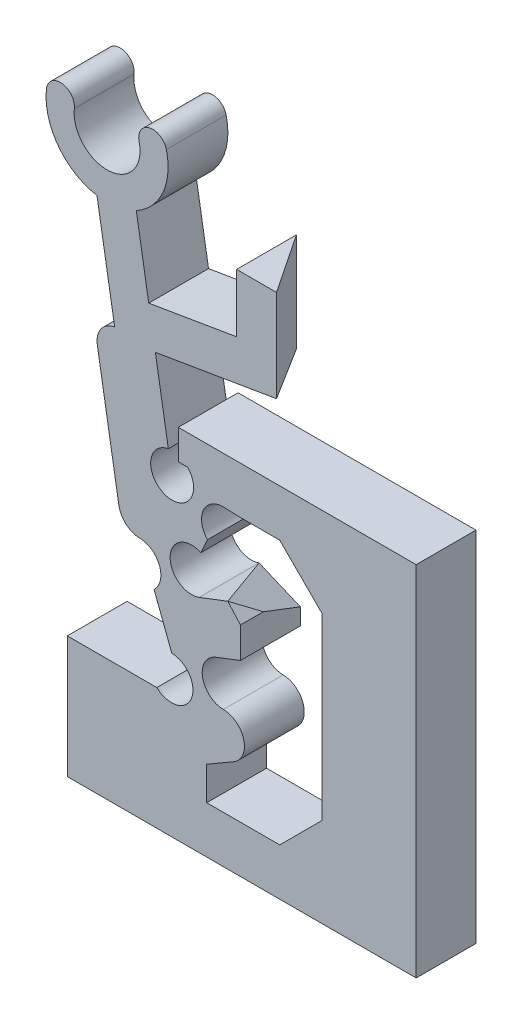
SolidWorks part; units mm, degrees
ref_plane "Front Plane" through (0, 0, 0) normal (0, 0, 1) x (1, 0, 0)
ref_plane "Top Plane" through (0, 0, 0) normal (0, 1, 0) x (1, 0, 0)
ref_plane "Right Plane" through (0, 0, 0) normal (1, 0, 0) x (0, 0, -1)
sketch "Sketch-SkeletonConfigUp" plane through (0, 0, 0) normal (0, 0, 1) x (1, 0, 0)
  line L0 (0, 0) -> (0, -50000) construction
  line L1 (0, 0) -> (4.5811, 6.2164) construction
  line L2 (9.8143, 13.3177) -> (4.5811, 13.945) construction
  line L3 (4.5811, 13.945) -> (2.9713, 10.4094) construction
  line L4 (2.9713, 10.4094) -> (4.5811, 6.2164) construction
  line L5 (4.5811, 13.945) -> (6.2429, 19.1409) construction
  line L6 (2.9713, 10.4094) -> (0.0405, 27.8193) construction
  line L7 (4.5811, 6.2164) -> (9.8143, 13.3177) construction
  line L8 (-587.3593, -797.0242) -> (9.8143, 13.3177) construction
  dimension "D2" = 7.7221
  dimension "D3" = 8.8212
  dimension "D4" = 5.2707
  dimension "D5" = 119.553
  dimension "D6" = 3.8848
  dimension "D7" = 5.4552
  dimension "D8" = 17.6549
  dimension "D9" = 4.4914
  dimension "D10" = 6.745
  dimension "D11" = 145.964
  dimension "D12" = 143.612
sketch "Sketch-SkeletonConfigDown" plane through (0, 0, 0) normal (0, 0, 1) x (1, 0, 0)
  line L0 (0, 0) -> (0, -50000) construction
  line L1 (0, 0) -> (4.5811, 6.2164) construction
  line L2 (9.8143, 13.3177) -> (4.5811, 13.945) construction
  line L3 (4.5811, 13.945) -> (6.1909, 10.4094) construction
  line L4 (6.1909, 10.4094) -> (4.5811, 6.2164) construction
  line L5 (4.5811, 13.945) -> (1.753, 18.6098) construction
  line L6 (6.1909, 10.4094) -> (-8.8652, 19.6294) construction
  line L7 (4.5811, 6.2164) -> (9.8143, 13.3177) construction
  line L8 (-589.9357, -800.5203) -> (9.8143, 13.3177) construction
  dimension "D2" = 7.7221
  dimension "D3" = 8.8212
  dimension "D4" = 5.2707
  dimension "D5" = 119.553
  dimension "D6" = 3.8848
  dimension "D7" = 5.4552
  dimension "D8" = 17.6549
  dimension "D9" = 4.4914
  dimension "D10" = 6.745
  dimension "D11" = 145.964
  dimension "D1" = 143.612
sketch "Sketch-SwitchBossUp" plane through (0, 0, 0) normal (0, 0, 1) x (1, 0, 0)
  line L0 (2.6478, 12.1123) -> (3.2566, 13.4492) construction
  line L1 (4.3447, 11.0125) -> (5.0768, 12.6205) construction
  line L2 (6.5405, 22.165) -> (6.5405, 25.0939)
  line L3 (6.5405, 25.0939) -> (8.5405, 25.0939)
  line L4 (8.5405, 25.0939) -> (8.5405, 20.4736)
  line L5 (4.5811, 13.945) -> (2.9713, 10.4094) construction
  line L7 (1.507, 25.1315) -> (2.1313, 21.4228)
  line L8 (-0.4652, 24.7995) -> (0.4213, 19.5329)
  line L9 (2.9713, 10.4094) -> (0.0405, 27.8193) construction
  line L10 (4.8917, 12.214) -> (3.0715, 13.0428) construction
  line L11 (-0.0396, 22.2712) -> (1.9326, 22.6032) construction
  line L13 (2.3961, 9.1174) -> (3.2891, 6.7916)
  line L14 (4.2633, 9.8343) -> (5.1563, 7.5084) construction
  line L15 (4.7098, 8.6713) -> (2.8426, 7.9545) construction
  line L16 (2.9713, 10.4094) -> (4.5811, 6.2164) construction
  line L17 (3.2566, 13.4492) -> (4.0854, 15.2694) construction
  line L18 (5.0768, 12.6205) -> (5.9056, 14.4407) construction
  line L19 (4.2853, 14.0796) -> (4.8769, 13.8103) construction
  line L20 (4.0854, 15.2694) -> (5.9056, 14.4407) construction
  line L21 (3.2566, 13.4492) -> (5.0768, 12.6205) construction
  line L22 (4.1667, 13.0349) -> (4.9955, 14.8551) construction
  line L23 (4.6678, 9.9058) -> (4.2913, 9.7612) construction
  line L24 (2.3961, 9.1174) -> (1.6793, 10.9845) construction
  line L25 (4.2633, 9.8343) -> (3.5464, 11.7014) construction
  line L26 (4.2633, 9.8343) -> (2.3961, 9.1174) construction
  line L27 (1.6793, 10.9845) -> (3.5464, 11.7014) construction
  line L28 (3.2891, 6.7916) -> (5.1563, 7.5084) construction
  line L29 (3.2891, 6.7916) -> (4.006, 4.9244) construction
  line L30 (5.1563, 7.5084) -> (5.8731, 5.6413) construction
  line L31 (4.006, 4.9244) -> (5.8731, 5.6413) construction
  line L32 (4.8845, 6.3329) -> (4.2777, 6.0999) construction
  line L36 (4.0854, 15.2694) -> (3.6136, 15.2694)
  line L40 (3.2747, 10.5259) -> (2.6679, 10.2929) construction
  line L43 (2.5363, 4.9244) -> (-1.9548, 4.9244)
  line L44 (-1.9548, 4.9244) -> (-1.9548, -1.1895)
  line L45 (-1.9548, -1.1895) -> (5.0405, -1.1895)
  line L46 (5.0405, 1.1715) -> (5.0405, 2.8478)
  line L51 (6.5405, 22.165) -> (2.1313, 21.4228)
  line L61 (6.6395, 14.4084) -> (6.6395, 16.7694) construction
  line L66 (0.0405, 27.8193) -> (0.0405, 50027.8193) construction
  line L73 (5.0768, 12.6205) -> (4.7428, 11.8869)
  line L74 (0.6325, 11.8929) -> (-0.448, 18.3116)
  line L75 (0.2173, 14.3595) -> (2.2273, 14.4682) construction
  line L76 (4.7428, 11.8869) -> (5.0768, 12.6205) construction
  line L77 (5.5047, 7.726) -> (5.1282, 7.5815) construction
  line L78 (4.6678, 9.9058) -> (6.094, 10.4534)
  line L79 (5.5047, 7.726) -> (6.4934, 8.1056)
  line L80 (6.094, 10.4534) -> (6.7341, 9.7424)
  line L81 (7.7675, 8.2601) -> (7.7675, -49991.7399) construction
  line L82 (2.1313, 21.4228) -> (3.1136, 15.5877) construction
  line L83 (3.1136, 15.5877) -> (2.4634, 19.4505)
  line L84 (2.4634, 19.4505) -> (8.5405, 20.4736)
  line L85 (6.9307, 9.5241) -> (7.7675, 8.5948) construction
  line L86 (6.4934, 8.1056) -> (6.7341, 8.198) construction
  line L88 (3.6136, 16.7694) -> (6.6395, 16.7694)
  line L90 (5.9056, 14.4407) -> (6.6395, 14.4084)
  line L92 (3.7762, 8.3129) -> (6.9307, 9.5241) construction
  line L93 (6.3942, 3.6294) -> (5.0405, 2.8478)
  line L94 (3.6136, 15.2694) -> (3.6136, 16.7694)
  line L95 (2.1313, 21.4228) -> (2.4634, 19.4505) construction
  line L96 (2.2974, 20.4367) -> (8.5405, 21.4876) construction
  line L97 (2.2974, 20.4367) -> (1.3112, 20.2707) construction
  line L98 (6.4934, 8.1056) -> (4.8199, 9.9642) construction
  line L99 (4.5811, 6.2164) -> (6.094, 10.4534) construction
  line L100 (4.5811, 6.2164) -> (8.5405, 8.3528) construction
  line L101 (4.5811, 6.2164) -> (6.9307, 9.5241) construction
  line L102 (4.5811, 6.2164) -> (8.5405, 7.1023) construction
  line L103 (8.5405, 20.4736) -> (8.5405, 8.3528) construction
  line L104 (6.9307, 9.5241) -> (7.7675, 8.5948) construction
  line L105 (6.7341, 8.198) -> (6.4934, 8.1056)
  line L106 (5.386, 8.3129) -> (8.5406, 7.1018) construction
  line L107 (6.1909, 10.4094) -> (4.5811, 6.2164) construction
  line L109 (6.9307, 8.2735) -> (7.7675, 8.5948) construction
  line L110 (7.7675, 8.5948) -> (6.9307, 8.2735) construction
  line L111 (6.7341, 9.7424) -> (6.7341, 8.198)
  line L112 (6.7341, 9.7424) -> (6.9307, 9.5241) construction
  line L113 (6.7341, 8.198) -> (6.9307, 8.2735) construction
  line L114 (6.9307, 8.2735) -> (6.7341, 8.198) construction
  line L115 (6.6395, 16.7694) -> (15.5467, 16.7694)
  line L116 (15.5467, 16.7694) -> (15.5467, -1.1895)
  line L117 (15.5467, -1.1895) -> (5.0405, -1.1895)
  line L118 (6.6395, 14.4084) -> (8.7032, 14.4084)
  line L119 (10.8245, 12.2871) -> (10.8245, 3.2928)
  line L120 (8.7032, 1.1715) -> (5.0405, 1.1715)
  line L121 (5.0405, -1.1895) -> (5.0405, 1.1715) construction
  line L122 (10.8245, 14.4084) -> (13.1856, 14.4084) construction
  line L123 (13.1856, 14.4084) -> (15.5467, 14.4084) construction
  line L124 (10.8245, 3.2928) -> (8.7032, 1.1715)
  line L125 (10.8245, 7.79) -> (15.5467, 7.79) construction
  line L126 (10.8245, 12.2871) -> (8.7032, 14.4084)
  line L127 (8.5405, 14.4084) -> (10.8245, 14.4084) construction
  line L128 (10.8245, 14.4084) -> (10.8245, 12.2871) construction
  line L129 (10.8245, 3.2928) -> (10.8245, 1.1715) construction
  line L130 (10.8245, 1.1715) -> (8.7032, 1.1715) construction
  arc A0 (1.507, 25.1315) -> (3.0168, 28.5383) centre (0.0405, 27.8193) ccw
  arc A1 (-0.4652, 24.7995) -> (-3.0011, 28.1713) centre (0.0405, 27.8193) cw
  arc A2 (-3.0011, 28.1713) -> (-1.6023, 28.0095) centre (-2.3017, 28.0904) cw
  arc A3 (3.0168, 28.5383) -> (1.648, 28.2077) centre (2.3324, 28.373) ccw
  arc A4 (-1.6023, 28.0095) -> (1.648, 28.2077) centre (0.0405, 27.8193) ccw
  arc A5 (3.2566, 13.4492) -> (4.0854, 15.2694) centre (3.304, 14.5264) ccw
  arc A6 (5.0768, 12.6205) -> (5.9056, 14.4407) centre (5.8582, 13.3635) cw
  arc A7 (2.3961, 9.1174) -> (1.6793, 10.9845) centre (1.6613, 9.9064) ccw
  arc A8 (3.5464, 11.7014) -> (4.2633, 9.8343) centre (4.2813, 10.9124) ccw
  arc A9 (3.2891, 6.7916) -> (4.006, 4.9244) centre (3.2711, 5.7135) cw
  arc A10 (5.1563, 7.5084) -> (5.8731, 5.6413) centre (5.8911, 6.7194) ccw
  arc A18 (1.6793, 10.9845) -> (0.6325, 11.8929) centre (1.6973, 12.0626) cw
  arc A19 (-0.448, 18.3116) -> (0.4213, 19.5329) centre (0.5973, 18.4876) cw
  arc A20 (3.2566, 13.4492) -> (3.1136, 15.5877) centre (3.304, 14.5264) cw
  arc A21 (4.006, 4.9244) -> (2.5363, 4.9244) centre (3.2711, 5.7135) cw
  arc A22 (5.8731, 5.6413) -> (6.3942, 3.6294) centre (5.8551, 4.5632) cw
  arc A24 (3.5464, 11.7014) -> (4.7428, 11.8869) centre (4.2813, 10.9124) cw
  arc A25 (4.2633, 9.8343) -> (4.6678, 9.9058) centre (4.2813, 10.9124) ccw
  arc A26 (5.1563, 7.5084) -> (5.5047, 7.726) centre (5.8911, 6.7194) cw
  arc A28 (6.3942, 3.6294) -> (5.2541, 3.668) centre (5.8551, 4.5632) cw construction
  point P44 (3.7762, 8.3129)
  point P53 (4.5811, 13.945)
  point P63 (2.9713, 10.4094)
  point P93 (0.9465, 22.4372)
  point P130 (0, 0)
  point P131 (0, 0)
  point P132 (0, 0)
  dimension "D1" = 2
  dimension "D2" = 2
  dimension "D3" = 2
  dimension "D4" = 2
  dimension "D5" = 2
  dimension "D6" = 0.65
  dimension "D7" = 2
  dimension "D8" = 42
  dimension "D9" = 0.5
  dimension "D10" = 5
  dimension "D11" = 8.5
  dimension "D12" = 120
  dimension "D13" = 1.5
  dimension "D14" = 10
  dimension "D15" = 45
  dimension "D16" = 42
  dimension "D17" = 42
  dimension "D18" = 3
extrude "Boss-SwitchMain" add sketch "Sketch-SwitchBossUp" along normal blind 3
sketch "Sketch1" plane through (0, 0, 0) normal (0, 0, -1) x (-1, 0, 0)
  line L0 (1.9548, 4.9244) -> (1.9548, -1.1895) construction
  line L1 (-4.628, -1.1895) -> (1.9548, -1.1895)
  line L2 (-4.628, -1.1895) -> (-4.628, 0.3105)
  line L3 (-4.628, 0.3105) -> (1.9548, 0.3105)
  line L4 (1.9548, -1.1895) -> (1.9548, 0.3105)
  line L5 (-3.6136, 16.7694) -> (-6.6395, 16.7694)
  line L6 (-2.5363, 4.9244) -> (1.9548, 4.9244)
  line L7 (-2.5363, 4.9244) -> (-2.5363, 3.4244)
  line L8 (-2.5363, 3.4244) -> (1.9548, 3.4244)
  line L9 (1.9548, 4.9244) -> (1.9548, 3.4244)
  line L10 (-6.6395, 16.7694) -> (-6.6395, 15.2694)
  line L12 (-6.6395, 15.2694) -> (-3.6136, 15.2694)
  line L13 (-5.128, -1.3839) -> (-5.128, 7.6731) construction
  line L14 (-3.6136, 15.2694) -> (-3.6136, 16.7694)
  line L18 (-3.6136, 16.7694) -> (-3.6136, 15.2694) construction
  line L19 (-5.128, -1.3839) -> (-5.128, 7.6731) construction
  line L20 (-6.6395, 16.7694) -> (-15.5467, 16.7694) construction
  line L21 (-6.6395, 14.4084) -> (-6.6395, 16.7694) construction
  point P16 (0, 0)
  point P21 (0, 0)
  point P22 (0, 0)
  dimension "D1" = 1.5
  dimension "D2" = 1.5
  dimension "D3" = 1.5
  dimension "D4" = 0.5
extrude "Boss-Flange Width" add sketch "Sketch1" along normal blind 6
ref_plane "Plane-Sta2Sit Groove" through (0.0405, 0, 0) normal (1, 0, 0) x (0, 0, -1)
ref_plane "Plane-Cam Face" through (-12.0395, 0, 0) normal (1, 0, 0) x (0, 0, -1)
ref_plane "Plane-FlangeTop" through (-7.0395, 0, 0) normal (1, 0, 0) x (0, 0, -1)
sketch "Sketch2" plane through (-7.0395, 0, 0) normal (1, 0, 0) x (0, 0, -1)
  line L0 (6, 15.2694) -> (-3, 15.2694) construction
  line L1 (6, 16.7694) -> (1, 16.7694)
  line L2 (6, 16.7694) -> (6, 15.2694)
  line L3 (6, 15.2694) -> (1, 15.2694)
  line L4 (1, 16.7694) -> (1, 15.2694)
  line L5 (6, 3.4244) -> (0, 3.4244) construction
  line L6 (6, 4.9244) -> (1, 4.9244)
  line L7 (6, 4.9244) -> (6, 3.4244)
  line L8 (6, 3.4244) -> (1, 3.4244)
  line L9 (1, 4.9244) -> (1, 3.4244)
  line L10 (-3, -1.1895) -> (6, -1.1895) construction
  line L11 (6, 0.3105) -> (1, 0.3105)
  line L12 (6, 0.3105) -> (6, -1.1895)
  line L13 (6, -1.1895) -> (1, -1.1895)
  line L14 (1, 0.3105) -> (1, -1.1895)
  line L15 (0, 10.4094) -> (0, 27.8193) construction
  dimension "D1" = 1
extrude "Boss-Flange Height" add sketch "Sketch2" along normal up to surface (11.6675 mm away)
sketch "Sketch-HolePositions" plane through (0, -1.1895, 0) normal (0, -1, 0) x (1, 0, 0)
  line L0 (-7.0395, -3.5) -> (4.628, -3.5) construction
  line L2 (4.628, -6) -> (4.628, 0) construction
  line L3 (-1.9548, -1) -> (-7.0395, -1) construction
  line L4 (-7.0395, -22.2167) -> (-7.0395, 22.2167) construction
  point P6 (-4.0395, -3.5)
  point P7 (1.628, -3.5)
  dimension "D1" = 3
  dimension "D2" = 3
  dimension "D3" = 2.5
sketch "Sketch6" plane through (0, -1.1895, 0) normal (0, -1, 0) x (-1, 0, 0)
  point P0 (4.0395, 3.5)
  point P3 (-1.628, 3.5)
hole_wizard "Tap Drill for M2x0.4 Tap1" positions "Sketch6" profile "Sketch5" hole size "M2x0.4" standard "ANSI Metric" end condition through all
sketch "Sketch5" plane through (-4.0395, -1.1895, -3.5) normal (1, 0, 0) x (0, 0, -1)
  line L0 (0, 0) -> (0, 30.2666)
  line L1 (0, 30.2666) -> (0.8, 30.2666)
  line L2 (0.8, 30.2666) -> (0.8, 0)
  line L5 (0.8, 0) -> (0, 0)
  line L11 (0, -6.35) -> (0, 107.95) construction
  dimension "Thru Hole Dia." = 1.6
  dimension "Thru Hole Depth" = 30.2666
sketch "Sketch9" plane through (0, -1.1895, 0) normal (0, -1, 0) x (1, 0, 0)
  point P0 (-4.0395, -3.5)
  point P3 (1.628, -3.5)
hole_wizard "M2 Clearance Hole2" positions "Sketch9" profile "Sketch8" hole size "M2" standard "ANSI Metric"
sketch "Sketch8" plane through (-4.0395, -1.1895, -3.5) normal (1, 0, 0) x (0, 0, -1)
  line L0 (0, 0) -> (0, 6.835)
  line L1 (0, 6.835) -> (1.2, 6.114)
  line L2 (1.2, 6.114) -> (1.2, 0)
  line L5 (1.2, 0) -> (0, 0)
  line L10 (0, 6.835) -> (-1.2, 6.114) construction
  line L11 (0, -6.35) -> (0, 107.95) construction
  dimension "Hole Dia." = 2.4
  dimension "Hole Depth" = 6.114
  dimension "Drill Angle" = 118
sketch "Sketch10" plane through (0, 16.7694, 0) normal (0, 1, 0) x (1, 0, 0)
  line L1 (6.6395, 6) -> (5.128, 6)
  line L2 (6.6395, 6) -> (6.6395, 3)
  line L3 (6.6395, 3) -> (5.128, 3)
  line L5 (4.628, 7) -> (4.628, 1) construction
  line L6 (3.6136, 1) -> (-7.0395, 1) construction
  line L7 (5.128, 6.25) -> (5.128, 1) construction
  line L8 (5.128, 6) -> (5.128, 3)
  point P1 (6.3963, 5.7235)
  point P13 (0, 0)
  dimension "D1" = 2
extrude "Cut-Flange Ramp Clearance" cut sketch "Sketch10" against normal up to next
sketch "Sketch-Measurements for Derailleur Ramps" plane through (0, 0, 0) normal (0, 0, 1) x (1, 0, 0)
  line L0 (2.4634, 19.4505) -> (2.1313, 21.4228)
  line L1 (2.2974, 20.4367) -> (1.3112, 20.2707)
  line L2 (2.9713, 10.4094) -> (0.0405, 27.8193) construction
  line L3 (1.3112, 20.2707) -> (-4.0257, 16.6658)
  line L4 (6.1909, 10.4094) -> (-8.8652, 19.6294) construction
  line L5 (1.3112, 20.2707) -> (2.6012, 12.6077)
  line L6 (2.6012, 12.6077) -> (-4.0257, 16.6658)
  line L7 (-1.3573, 18.4682) -> (-1.3573, 20.2707)
  line L8 (-1.3573, 20.2707) -> (1.3112, 20.2707)
  line L9 (6.1909, 10.4094) -> (2.9713, 10.4094)
  line L10 (5.386, 8.3129) -> (3.7762, 8.3129)
  line L12 (6.1909, 10.4094) -> (4.5811, 6.2164) construction
  line L13 (4.5811, 8.3129) -> (4.5811, 8.7912)
  line L14 (4.5811, 6.2164) -> (5.386, 8.3129)
  line L15 (2.9713, 10.4094) -> (4.5811, 6.2164) construction
  line L16 (3.7762, 8.3129) -> (4.5811, 6.2164)
  line L17 (5.386, 8.3129) -> (5.386, 8.7912)
  dimension "D1" = 2.6685
  dimension "D2" = 0.8049
sketch "Sketch12" plane through (0, 25.0939, 0) normal (0, 1, 0) x (1, 0, 0)
  line L0 (6.5405, 0) -> (8.5405, -3)
  line L1 (8.5405, -3) -> (8.5405, 0)
  line L2 (8.5405, 0) -> (6.5405, 0)
extrude "Cut-Extrude1" cut sketch "Sketch12" against normal up to next
ref_plane "Plane1" through (0, 7.1023, 0) normal (0, 1, 0) x (1, 0, 0)
sketch "Sketch-Derailleur Location" plane through (0, 7.1023, 0) normal (0, 1, 0) x (1, 0, 0)
  line L0 (8.5405, 0) -> (8.5405, -3)
  line L1 (2.2257, -3) -> (4.3822, -3) construction
  point P0 (8.5405, 0)
  point P8 (8.5405, -1.5)
ref_plane "Plane-Cantilever Cut" through (3.7891, 8.959, -3.4367) normal (-0.3673, -0.8684, 0.3331) x (-0.9301, 0.3429, -0.1315)
sketch "Sketch14" plane through (3.7891, 8.959, -3.4367) normal (-0.3673, -0.8684, 0.3331) x (-0.9301, 0.3429, -0.1315)
  line L0 (-0.9447, -3.5478) -> (-4.2773, -3.0783)
  line L2 (-1.432, -6.9644) -> (-0.9447, -3.5478)
  line L3 (-4.2773, -3.0783) -> (-4.8248, -6.9644)
  line L4 (-4.8248, -6.9644) -> (-1.432, -6.9644)
extrude "Cut-Extrude2" cut sketch "Sketch14" against normal up to next
sketch "Sketch15" plane through (0, 0, 0) normal (0, 0, -1) x (-1, 0, 0)
  line L1 (-10.0534, 18.2157) -> (8.3706, 18.2157)
  line L2 (-10.0534, 18.2157) -> (-10.0534, -2.1599)
  line L3 (-10.0534, -2.1599) -> (8.3706, -2.1599)
  line L4 (8.3706, 18.2157) -> (8.3706, -2.1599)
extrude "Cut-Extrude3" cut sketch "Sketch15" along normal through all
equation "\"axle-diameter\"=2"
equation "\"switch-thickness\"=12"
equation "\"base-width\"=4.0"
equation "\"axle-bushing-radius\"=3"
equation "\"clearance\"= 0.25"
equation "\"arm-width\"=1.5"
equation "\"min-diameter\"=70"
equation "\"alpha\"=143.6120"
equation "\"gamma\"=119.5526"
equation "\"delta\"=145.9637"
equation "\"epsilon\"=6.7452"
equation "\"l_AB\"=8.8212"
equation "\"l_AC\"=4.4914"
equation "\"l_BD\"=5.2707"
equation "\"l_CD\"=3.8848"
equation "\"l_CE\"=17.6549"
equation "\"l_DF\"=5.4552"
equation "\"l_OA\"=7.7221"
equation "\"D2@Sketch-SkeletonConfigUp\" = \"l_OA\""
equation "\"D3@Sketch-SkeletonConfigUp\" = \"l_AB\""
equation "\"D4@Sketch-SkeletonConfigUp\" = \"l_BD\""
equation "\"D5@Sketch-SkeletonConfigUp\" = \"gamma\""
equation "\"D6@Sketch-SkeletonConfigUp\" = \"l_CD\""
equation "\"D7@Sketch-SkeletonConfigUp\" = \"l_DF\""
equation "\"D8@Sketch-SkeletonConfigUp\" = \"l_CE\""
equation "\"D9@Sketch-SkeletonConfigUp\" = \"l_AC\""
equation "\"D_groove\"=3.175"
equation "\"D7@Sketch-SkeletonConfigDown\" = \"l_DF\""
equation "\"D6@Sketch-SkeletonConfigDown\" = \"l_CD\""
equation "\"D2@Sketch-SkeletonConfigDown\" = \"l_OA\""
equation "\"D3@Sketch-SkeletonConfigDown\" = \"l_AB\""
equation "\"D9@Sketch-SkeletonConfigDown\" = \"l_AC\""
equation "\"D8@Sketch-SkeletonConfigDown\" = \"l_CE\""
equation "\"D5@Sketch-SkeletonConfigDown\" = \"gamma\""
equation "\"D4@Sketch-SkeletonConfigDown\" = \"l_BD\""
equation "\"D1@Sketch-SkeletonConfigDown\" = \"alpha\""
equation "\"hinge_length\"=1.5"
equation "\"hinge_depth\"=0.25"
equation "\"D10@Sketch-SkeletonConfigUp\"=\"epsilon\""
equation "\"D11@Sketch-SkeletonConfigUp\"=\"delta\""
equation "\"D12@Sketch-SkeletonConfigUp\"=\"alpha\""
equation "\"D11@Sketch-SkeletonConfigDown\"=\"delta\""
equation "\"D10@Sketch-SkeletonConfigDown\"=\"epsilon\""
equation "\"EE_dx\"=8.9056"
equation "\"EE_dy\"=8.1898"
equation "\"r_groove\"=\"D_groove\"/2"
equation "\"t_wall\"=25.4/16"
equation "\"width_lower\"=\"D_groove\"+\"t_wall\""
equation "\"cable_to_bottom\"=30.6257"
equation "\"switch_EE-up_base_dy\"=24"
equation "\"switch_EE-down_base_dy\"=16"
equation "\"D_axle\"=25.4/8"
equation "\"D_up_to_down\"=16"
equation "\"D_down_to_up\"=25"
equation "\"t_cam_base\"=7.5"
